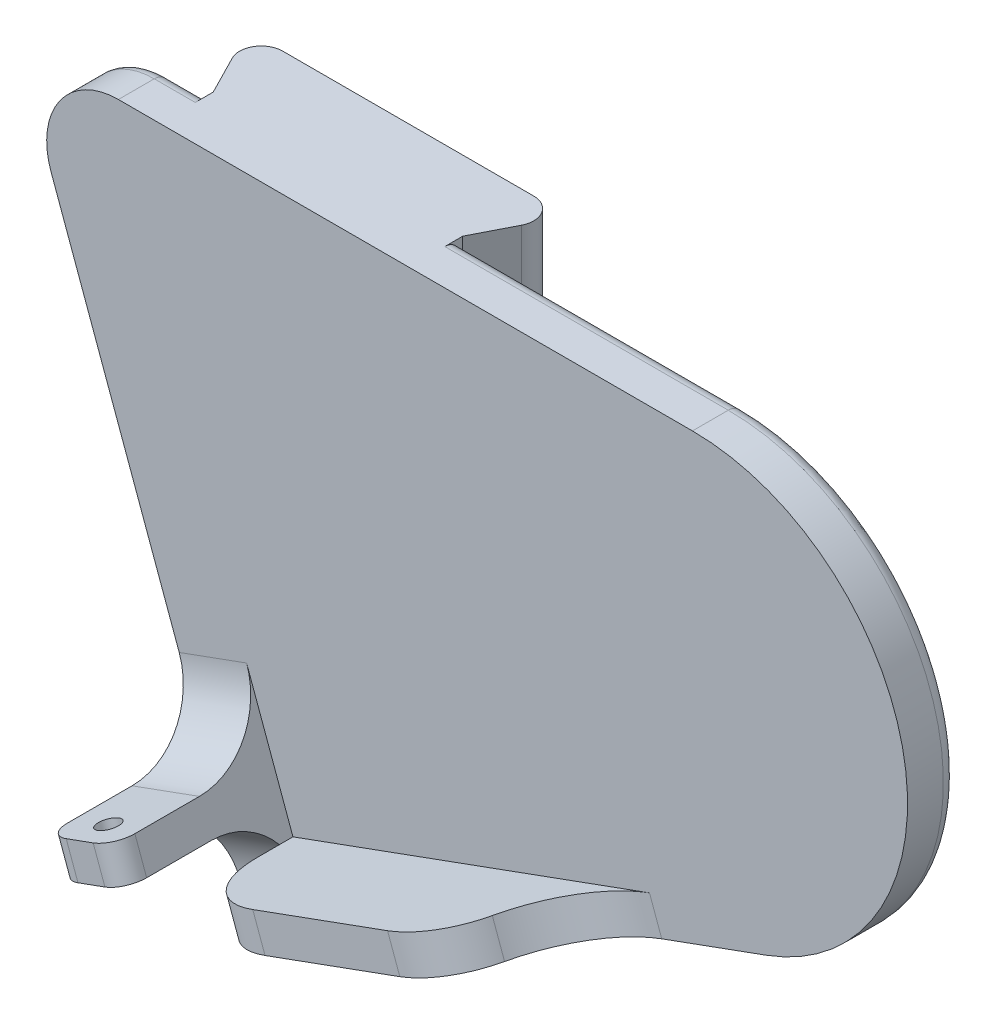
SolidWorks part; units mm, degrees
ref_plane "Alzado" through (0, 0, 0) normal (0, 0, 1) x (1, 0, 0)
ref_plane "Planta" through (0, 0, 0) normal (0, 1, 0) x (1, 0, 0)
ref_plane "Vista lateral" through (0, 0, 0) normal (1, 0, 0) x (0, 0, -1)
sketch "Croquis1" plane through (0, 0, 0) normal (0, 1, 0) x (1, 0, 0)
  line L0 (-20.1738, -4.3634) -> (-17.4, -9.8)
  line L1 (17.4, -9.8) -> (-17.4, -9.8) construction
  line L3 (17.5015, 0) -> (-17.5015, 0)
  line L5 (20.1738, -4.3634) -> (17.4, -9.8)
  line L8 (-17.4, -9.8) -> (-17.4, -10.3)
  line L9 (-17.4, -10.3) -> (17.4, -10.3)
  line L10 (17.4, -9.8) -> (17.4, -10.3)
  arc A0 (20.1738, -4.3634) -> (17.5015, 0) centre (17.5015, -3) ccw
  arc A1 (-17.5015, 0) -> (-20.1738, -4.3634) centre (-17.5015, -3) ccw
  point P0 (0, 0)
  point P2 (0, -9.8)
  point P6 (0, 0)
  point P8 (22.4, 0)
  point P13 (-22.4, 0)
  point P17 (0, 0)
  dimension "D4" = 3
  dimension "D1" = 9.8
  dimension "D2" = 44.8
  dimension "D3" = 5
  dimension "D5" = 0.5
extrude "Saliente-Extruir1" add sketch "Croquis1" along normal blind 18
sketch "Croquis2" plane through (0, 0, 10.3) normal (0, 0, 1) x (1, 0, 0)
  line L0 (-17.4, 18) -> (-23.1185, 18)
  line L1 (-32.5154, 4.5798) -> (-6.4625, -67)
  line L2 (-6.4625, -67) -> (67.1952, -40.1908)
  line L3 (-17.4, 18) -> (56.9346, 18)
  arc A0 (67.1952, -40.1908) -> (56.9346, 18) centre (56.9346, -12) ccw
  arc A1 (-23.1185, 18) -> (-32.5154, 4.5798) centre (-23.1185, 8) ccw
  point P9 (-37.4, 18)
  dimension "D2" = 30
  dimension "D5" = 10
  dimension "D1" = 20
  dimension "D3" = 85
  dimension "D4" = 20
extrude "Saliente-Extruir2" add sketch "Croquis2" along normal blind 7
sketch "Croquis4" plane through (-27.2399, -9.9145, 0) normal (-0.9397, -0.342, 0) x (0, 0, 1)
  line L0 (17.3, 15.4245) -> (17.3, -60.7491) construction
  line L1 (17.3, -46.8491) -> (39.3, -46.8491)
  line L2 (17.3, -46.8491) -> (17.3, -51.6491)
  line L3 (17.3, -51.6491) -> (39.3, -51.6491)
  line L4 (39.3, -46.8491) -> (39.3, -51.6491)
  dimension "D1" = 22
  dimension "D2" = 4.8
  dimension "D3" = 9.1
extrude "Saliente-Extruir3" add sketch "Croquis4" against normal blind 10
fillet "Redondeo1" radius 10 2 edges at (-6.5181, -52.2282, 17.3) (-4.8765, -56.7387, 17.3)
fillet "Redondeo2" radius 3 2 edges at (-0.9988, -52.7733, 39.3) (-10.3958, -56.1935, 39.3)
sketch "Croquis5" plane through (17.665, -48.5343, 0) normal (0.342, -0.9397, 0) x (0.9397, 0.342, 0)
  line L0 (-21.9881, 39.3) -> (-25.9881, 39.3) construction
  circle A0 centre (-23.9881, 35.3) radius 1.5
  point P4 (-23.9881, 39.3)
  dimension "D2" = 3
  dimension "D1" = 4
extrude "Cortar-Extruir1" cut sketch "Croquis5" against normal through all
sketch "Croquis6" plane through (20.7774, -57.0855, 0) normal (0.342, -0.9397, 0) x (0.9397, 0.342, 0)
  line L1 (-18.9881, 17.3) -> (21.0119, 17.3)
  line L2 (-18.9881, 17.3) -> (-18.9881, 32.3)
  line L3 (-18.9881, 32.3) -> (21.0119, 32.3)
  line L4 (21.0119, 17.3) -> (21.0119, 32.3)
  point P5 (0, 0)
  point P6 (-34.3792, 17.3)
  point P7 (0, 0)
  dimension "D1" = 40
  dimension "D2" = 15
extrude "Saliente-Extruir4" add sketch "Croquis6" against normal blind 5
fillet "Redondeo3" radius 10 2 edges at (2.0793, -61.2306, 32.3) (39.6671, -47.5498, 32.3)
fillet "Redondeo4" radius 15 1 edges at (39.6671, -47.5498, 17.3)
fillet "Redondeo5" radius 2 6 edges at (37.1673, 18, 10.3) (86.4788, -6.7906, 10.3) (-20.2593, 18, 10.3) (-31.31, 13.7358, 10.3) (30.3663, -53.5954, 10.3) (-19.489, -31.2101, 10.3)
